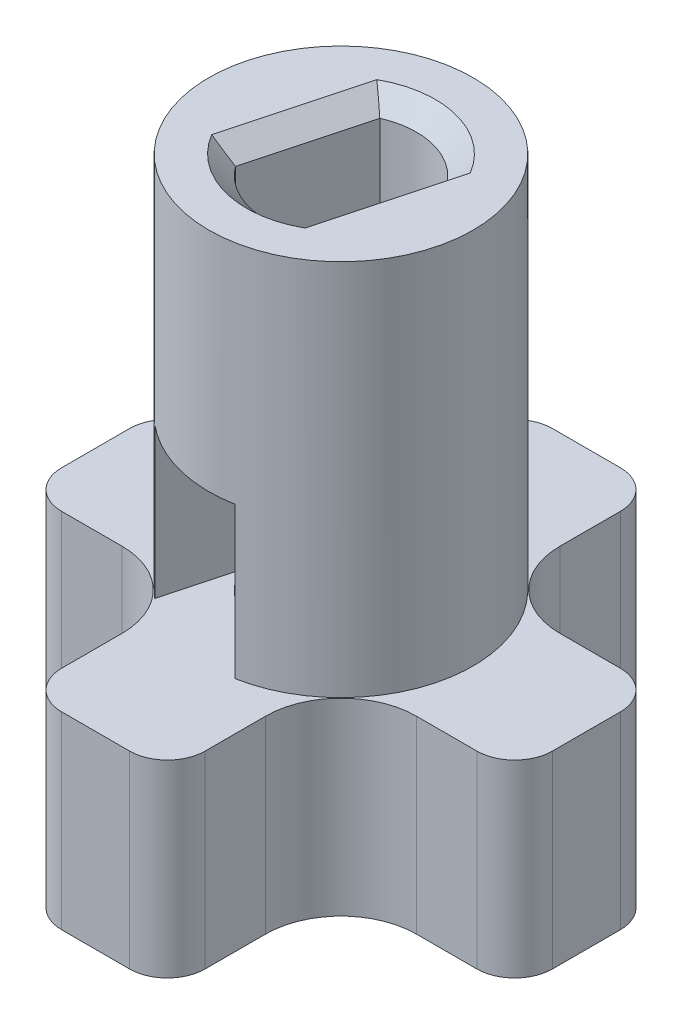
SolidWorks part; units mm, degrees
ref_plane "前视基准面" through (0, 0, 0) normal (0, 0, 1) x (1, 0, 0)
ref_plane "上视基准面" through (0, 0, 0) normal (0, 1, 0) x (1, 0, 0)
ref_plane "右视基准面" through (0, 0, 0) normal (1, 0, 0) x (0, 0, -1)
sketch "草图1" plane through (0, 0, 0) normal (0, 1, 0) x (1, 0, 0)
  circle A0 centre (0, 0) radius 3.5
  dimension "D1" = 7
extrude "凸台-拉伸1" add sketch "草图1" along normal blind 15
sketch "草图2" plane through (0, 0, 0) normal (0, -1, 0) x (1, 0, 0)
  line L0 (0, 0) -> (0, 6.5) construction
  line L1 (0.9, 6.5) -> (-0.9, 6.5)
  line L2 (6.5, -0.9) -> (6.5, 0.9)
  line L3 (-0.9, -6.5) -> (0.9, -6.5)
  line L4 (-6.5, 0.9) -> (-6.5, -0.9)
  line L5 (-5.5, 1.9) -> (-3.9, 1.9)
  line L6 (-5.5, -1.9) -> (-3.9, -1.9)
  line L7 (-1.9, 5.5) -> (-1.9, 3.9)
  line L8 (1.9, 5.5) -> (1.9, 3.9)
  line L9 (3.9, 1.9) -> (5.5, 1.9)
  line L10 (-1.9, -3.9) -> (-1.9, -5.5)
  line L11 (3.9, -1.9) -> (5.5, -1.9)
  line L12 (1.9, -3.9) -> (1.9, -5.5)
  arc A0 (3.9, -1.9) -> (1.9, -3.9) centre (3.9, -3.9) ccw
  arc A1 (-1.9, -3.9) -> (-3.9, -1.9) centre (-3.9, -3.9) ccw
  arc A2 (3.9, 1.9) -> (1.9, 3.9) centre (3.9, 3.9) cw
  arc A3 (-3.9, 1.9) -> (-1.9, 3.9) centre (-3.9, 3.9) ccw
  arc A4 (0.9, -6.5) -> (1.9, -5.5) centre (0.9, -5.5) ccw
  arc A5 (-0.9, -6.5) -> (-1.9, -5.5) centre (-0.9, -5.5) cw
  arc A6 (6.5, -0.9) -> (5.5, -1.9) centre (5.5, -0.9) cw
  arc A7 (6.5, 0.9) -> (5.5, 1.9) centre (5.5, 0.9) ccw
  arc A8 (-6.5, -0.9) -> (-5.5, -1.9) centre (-5.5, -0.9) ccw
  arc A9 (-6.5, 0.9) -> (-5.5, 1.9) centre (-5.5, 0.9) cw
  arc A10 (1.9, 5.5) -> (0.9, 6.5) centre (0.9, 5.5) ccw
  arc A11 (-0.9, 6.5) -> (-1.9, 5.5) centre (-0.9, 5.5) ccw
  point P14 (0, 0)
  point P18 (1.9, -1.9)
  point P27 (1.9, -6.5)
  point P40 (1.9, 6.5)
  point P43 (-1.9, 6.5)
  dimension "D6" = 2
  dimension "D7" = 1
  dimension "D1" = 6.5
  dimension "D2" = 1.9
  dimension "D3" = 4
  dimension "D4" = 6.5
  dimension "D5" = 1.9
extrude "凸台-拉伸2" add sketch "草图2" against normal blind 5
sketch "草图3" plane through (0, 15, 0) normal (0, 1, 0) x (1, 0, 0)
  line L0 (0, 0) -> (0, 2) construction
  line L1 (0, 0) -> (0.5176, 1.9319) construction
  line L2 (0, 0) -> (-0.5176, -1.9319) construction
  line L3 (1.2074, -0.3235) -> (0.8033, -1.8316)
  line L4 (1.2074, -0.3235) -> (1.6115, 1.1845)
  line L5 (-1.2074, 0.3235) -> (-1.6115, -1.1845)
  line L6 (-1.2074, 0.3235) -> (-0.8033, 1.8316)
  line L8 (-1.2074, 0.3235) -> (-0.6898, 2.2554) construction
  line L9 (1.2074, -0.3235) -> (1.725, 1.6083) construction
  line L10 (1.2074, -0.3235) -> (0.6898, -2.2554) construction
  line L11 (-1.2074, 0.3235) -> (-1.725, -1.6083) construction
  arc A0 (-1.6115, -1.1845) -> (0.8033, -1.8316) centre (0, 0) ccw
  arc A1 (1.6115, 1.1845) -> (-0.8033, 1.8316) centre (0, 0) ccw
  dimension "D1" = 4
  dimension "D2" = 15
  dimension "D3" = 1.25
  dimension "D4" = 1.25
extrude "切除-拉伸1" cut sketch "草图3" against normal blind 15
sketch "草图4" plane through (0, 0, 0) normal (1, 0, 0) x (0, 0, -1)
  line L0 (0, 0) -> (0, 15) construction
  line L1 (3.5, 15) -> (-3.5, 15) construction
ref_plane "基准面1" through (0, 0, 0) normal (0.2588, 0, -0.9659) x (-0.9659, 0, -0.2588)
sketch "草图5" plane through (0, 0, 0) normal (0.2588, 0, -0.9659) x (-0.9659, 0, -0.2588)
  line L0 (0, 0) -> (0, 5) construction
  line L1 (0, 0) -> (0, 15) construction
  line L2 (0.813, 5) -> (-0.4118, 5) construction
  line L3 (0, 5) -> (0, 9) construction
  line L4 (-1.5, 9) -> (1.5, 9)
  line L5 (1.5, 9) -> (1.5, 5)
  line L6 (2.5517, 5) -> (0.813, 5) construction
  line L7 (1.5, 5) -> (-1.5, 5)
  line L8 (-1.5, 9) -> (-1.5, 5)
  dimension "D1" = 4
  dimension "D2" = 1.5
extrude "切除-拉伸2" cut sketch "草图5" against normal blind 15 and the other way blind 15
chamfer "倒角1" distance 0.5 angle 45 8 edges at (1.2074, 0, 0.3235) (0.5176, 0, -1.9319) (-1.2074, 0, -0.3235) (-0.5176, 0, 1.9319) (-0.5176, 15, 1.9319) (-1.2074, 15, -0.3235) (0.5176, 15, -1.9319) (1.2074, 15, 0.3235)
